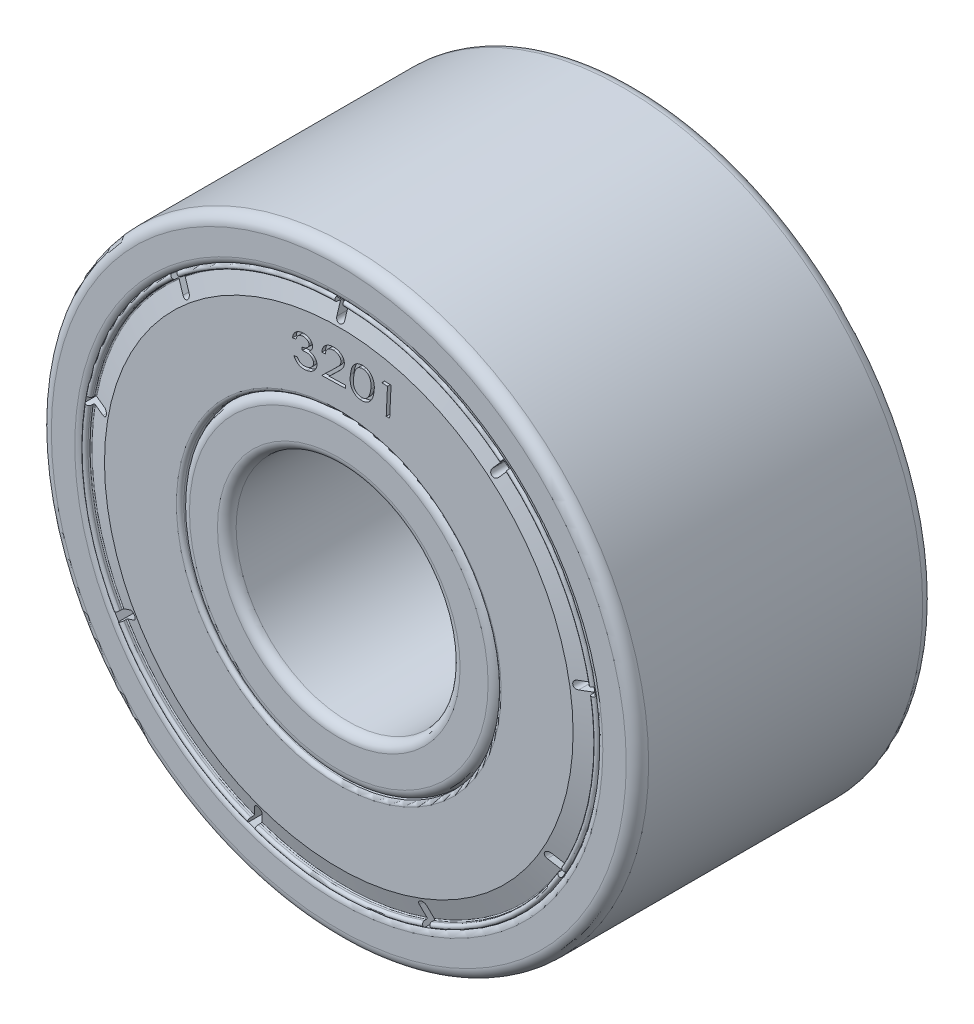
SolidWorks part; units mm, degrees
other "OD"
other "ID"
ref_plane "Front Plane" through (0, 0, 0) normal (0, 0, 1) x (1, 0, 0)
ref_plane "Top Plane" through (0, 0, 0) normal (0, 1, 0) x (1, 0, 0)
ref_plane "Right Plane" through (0, 0, 0) normal (1, 0, 0) x (0, 0, -1)
sketch "Sketch1" plane through (0, 0, 0) normal (0, 0, 1) x (1, 0, 0)
  circle A0 centre (0, 0) radius 16
  circle A1 centre (0, 0) radius 6
  circle A2 centre (0, 0) radius 8.5
  circle A3 centre (0, 0) radius 13.85
  dimension "D1" = 32
  dimension "D2" = 12
  dimension "D3" = 17
  dimension "D4" = 27.7
extrude "Rings" add sketch "Sketch1" against normal blind 15.88 contours A0 | A3 | A2 | A1
sketch "Sketch3" plane through (0, 0, 0) normal (0, 1, 0) x (1, 0, 0)
  line L0 (0, 0) -> (0, 15.88) construction
  line L1 (16, 15.88) -> (-16, 15.88) construction
ref_axis "Axis1" through (0, 0, -15.88) along (0, 0, 1)
fillet "Fillet2" radius 0.5 4 edges at (6, 0, -15.88) (8.5, 0, -15.88) (6, 0, 0) (8.5, 0, 0)
sketch "Sketch5" plane through (0, 0, 0) normal (0, 1, 0) x (1, 0, 0)
  line L0 (-16, 0) -> (16, 0) construction
  line L1 (-13.85, 0) -> (13.85, 0) construction
  line L4 (8.7, 0) -> (12.5526, 0)
  line L5 (13.5787, 0.1402) -> (13.5787, 0.2483)
  line L7 (8.5, 0.2) -> (8.5, 4)
  line L8 (13.8503, 0.1402) -> (13.8503, 4)
  line L11 (13.514, 0.2961) -> (12.5526, 0)
  line L15 (8.5, 4) -> (13.8503, 4)
  arc A0 (13.8503, 0.1402) -> (13.5787, 0.1402) centre (13.7145, 0.1402) cw
  arc A1 (8.5, 0.2) -> (8.7, 0) centre (8.7, 0.2) ccw
  arc A2 (13.514, 0.2961) -> (13.5787, 0.2483) centre (13.5287, 0.2483) cw
  point P16 (12.5526, 0)
  dimension "D1" = 0.2
  dimension "D2" = 0.05
  dimension "D3" = 4
revolve "Balls cover" add sketch "Sketch5" angle 360 about L0
ref_plane "Plane1" through (0, 0, -7.94) normal (0, 0, 1) x (1, 0, 0)
fillet "Fillet6" radius 0.6 2 edges at (16, 0, 0) (16, 0, -15.88)
mirror "Mirror12" about plane through (0, 0, -7.94) normal (0, 0, 1) of "Balls cover"
sketch "Sketch12" plane through (0, 0, 0) normal (0, 0, 1) x (1, 0, 0)
  line L0 (0, 13.8361) -> (0, 8.6153) construction
  line L2 (0.2116, 13.8361) -> (0.2116, 12.8973)
  line L3 (-0.2116, 13.8361) -> (-0.2116, 12.8973)
  line L4 (-0.2116, 13.8361) -> (0.2116, 13.8361)
  arc A2 (-0.2116, 12.8973) -> (0.2116, 12.8973) centre (0, 12.8973) ccw
  point P2 (0, 13.8361)
extrude "Slots" cut sketch "Sketch12" against normal through all contours L3 A2 L2 L4
pattern_circular "CirPattern6" count 9 over 360 of "Slots"
fillet "Fillet10" radius 0.4 2 edges at (13.85, 0, 0) (13.85, 0, -15.88)
sketch "Sketch28" plane through (0, 0, 0) normal (0, 0, 1) x (1, 0, 0)
  line L0 (0, 13.8361) -> (0, 8.6153) construction
  arc A0 (-2.4184, 9.5953) -> (2.4184, 9.5953) centre (0, 0) cw construction
  text T0 "3201" font "Century Gothic" height in points 6
  point P5 (0, 9.8954)
extrude "Cut-Extrude1" cut sketch "Sketch28" against normal blind 0.2
